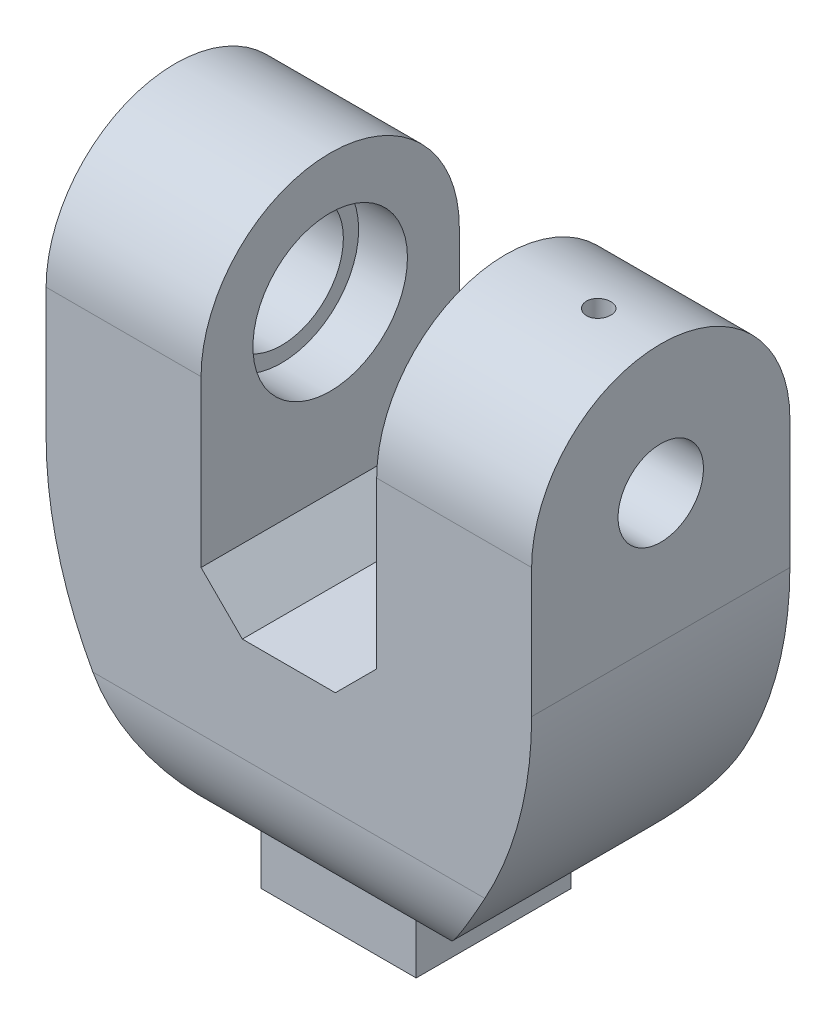
SolidWorks part; units mm, degrees
material "PLA"
ref_plane "Front Plane" through (0, 0, 0) normal (0, 0, 1) x (1, 0, 0)
ref_plane "Top Plane" through (0, 0, 0) normal (0, 1, 0) x (1, 0, 0)
ref_plane "Right Plane" through (0, 0, 0) normal (1, 0, 0) x (0, 0, -1)
sketch "Sketch1" plane through (0, 0, 0) normal (1, 0, 0) x (0, 0, -1)
  circle A0 centre (0, 0) radius 3 construction
  circle A1 centre (0, 0) radius 9.5
  circle A2 centre (0, 0) radius 15.875
  dimension "D1" = 6
  dimension "D2" = 19
  dimension "D3" = 31.75
extrude "Boss-Extrude1" add sketch "Sketch1" along normal blind 6
sketch "Sketch2" plane through (0, 0, 0) normal (-1, 0, 0) x (0, 0, 1)
  circle A0 centre (0, 0) radius 9.5 construction
  circle A1 centre (0, 0) radius 15.875
  circle A2 centre (0, 0) radius 15.875
  circle A3 centre (0, 0) radius 9.5
  circle A4 centre (0, 0) radius 7.62
  circle M3 centre (0, 0) radius 15.875
  circle M4 centre (0, 0) radius 9.5
  dimension "D2" = 15.24
  dimension "D1" = 0
extrude "Boss-Extrude2" add sketch "Sketch2" along normal blind 13.05 contours A4 M4 | M3 M4 region at (0, 0, -15.426) region at (0, 0, -9.2313)
ref_plane "Plane1" through (16.795, 0, 0) normal (1, 0, 0) x (0, 0, -1)
mirror "Mirror2" about plane through (16.795, 0, 0) normal (1, 0, 0) of bodies 102
sketch "Sketch3" plane through (6, 0, 0) normal (1, 0, 0) x (0, 0, -1)
  line L0 (-15.875, 0) -> (-15.875, -38.1)
  line L1 (15.875, 0) -> (15.875, -38.1)
  arc A0 (-15.875, -38.1) -> (15.875, -38.1) centre (0, -38.1) ccw
  circle A1 centre (0, 0) radius 15.875
  circle A2 centre (0, 0) radius 15.875
  circle M2 centre (0, 0) radius 15.875
  dimension "D2" = 38.1
  dimension "D3" = 15.875
  dimension "D1" = 0
extrude "Boss-Extrude3" add sketch "Sketch3" against normal up to surface (19.05 mm away) contours L0 A0 L1 M2 region at (6, -31.5182, 0) up to face at (-13.05, 0, 7.62)
extrude "Boss-Extrude4" add sketch "Sketch3<3>" along normal up to surface (40.64 mm away) from surface contours L0 A0 L1 M2 region at (6, -31.5182, 0) up to face at (46.64, 0, 7.62) starting at face at (27.59, 0, -15.875)
sketch "Sketch3<3>" plane through (6, 0, 0) normal (1, 0, 0) x (0, 0, -1) same geometry as "Sketch3"
sketch "Sketch4" plane through (6, 0, 0) normal (1, 0, 0) x (0, 0, -1)
  line L0 (-15.875, -25.4) -> (15.875, -25.4)
  line L2 (-15.875, 0) -> (-15.875, -38.1)
  line L3 (15.875, -38.1) -> (15.875, 0)
  line L4 (-15.875, 0) -> (-15.875, -38.1)
  line L5 (15.875, -38.1) -> (15.875, 0)
  arc A2 (15.875, 0) -> (-15.875, 0) centre (0, 0) ccw
  arc A3 (-15.875, -38.1) -> (15.875, -38.1) centre (0, -38.1) ccw
  arc A4 (15.875, 0) -> (-15.875, 0) centre (0, 0) ccw
  arc A5 (-15.875, -38.1) -> (15.875, -38.1) centre (0, -38.1) ccw
  line M7 (-15.875, 0) -> (-15.875, -38.1)
  arc M8 (-15.875, -38.1) -> (15.875, -38.1) centre (0, -38.1) ccw
  line M9 (15.875, -38.1) -> (15.875, 0)
  dimension "D2" = 25.4
  dimension "D1" = 0
extrude "Boss-Extrude5" add sketch "Sketch4" along normal up to surface (21.59 mm away) contours L0 M7 M8 M9 region at (6, -38.2335, 0) up to face at (27.59, -19.05, 0)
sketch "Sketch5" plane through (0, 0, 15.875) normal (0, 0, 1) x (1, 0, 0)
  line L0 (6, -15.875) -> (-13.05, -15.875) construction
  line L2 (-13.05, -38.1) -> (-13.05, -53.975) construction
  line L8 (6, 0) -> (-13.05, 0)
  line L9 (-13.05, 0) -> (-13.05, -38.1)
  line L10 (-13.05, -38.1) -> (46.64, -38.1)
  line L11 (46.64, -38.1) -> (46.64, 0)
  line L12 (46.64, 0) -> (27.59, 0)
  line L13 (27.59, 0) -> (27.59, -25.4)
  line L14 (27.59, -25.4) -> (6, -25.4)
  line L15 (6, -25.4) -> (6, 0)
  line L16 (6, 0) -> (-13.05, 0)
  line L17 (-13.05, 0) -> (-13.05, -38.1)
  line L18 (-13.05, -38.1) -> (46.64, -38.1)
  line L19 (46.64, -38.1) -> (46.64, 0)
  line L20 (46.64, 0) -> (27.59, 0)
  line L21 (27.59, 0) -> (27.59, -25.4)
  line L22 (27.59, -25.4) -> (6, -25.4)
  line L23 (6, -25.4) -> (6, 0)
  line L25 (-13.05, -38.1) -> (-13.05, -53.975)
  line L26 (-13.05, -53.975) -> (46.64, -53.975)
  line L27 (46.64, -53.975) -> (46.64, -38.1)
  line L28 (-13.05, -15.875) -> (7.27, -53.975)
  line L29 (46.64, -15.875) -> (26.32, -53.975)
  line L30 (-13.05, -53.975) -> (46.64, -53.975) construction
  line L31 (16.795, -17.4625) -> (16.795, 17.4625) construction
  arc A0 (-13.05, -15.875) -> (7.27, -53.975) centre (32.8287, -15.875) ccw
  arc A1 (46.64, -15.875) -> (26.32, -53.975) centre (0.7613, -15.875) cw
  line M14 (-13.05, -38.1) -> (46.64, -38.1)
  line M15 (46.64, -38.1) -> (46.64, 0)
  dimension "D2" = 15.875
  dimension "D3" = 19.05
  dimension "D1" = 0
extrude "Cut-Extrude1" cut sketch "Sketch5" against normal through all contours L28 L25 L26 M14 | L28 L17 M14 | L29 L26 L27 M14 | L29 M15 M14 region at (-11.3474, -32.6157, 15.875) region at (-6.3907, -47.6285, 15.875) region at (44.9374, -32.6157, 15.875) region at (39.9807, -47.6285, 15.875)
sketch "Sketch9" plane through (0, -25.4, 0) normal (0, 1, 0) x (1, 0, 0)
  line L0 (5.7854, 0) -> (27.3575, 0) construction
  line L1 (16.795, 15.875) -> (16.795, -15.875) construction
  line L2 (27.59, 15.875) -> (6, 15.875) construction
  line L4 (27.59, -15.875) -> (27.59, 15.875)
  line L5 (27.59, 15.875) -> (6, 15.875)
  line L6 (6, 15.875) -> (6, -15.875)
  line L7 (6, -15.875) -> (27.59, -15.875)
  line L8 (27.59, -15.875) -> (27.59, 15.875)
  line L9 (27.59, 15.875) -> (6, 15.875)
  line L10 (6, 15.875) -> (6, -15.875)
  line L11 (6, -15.875) -> (27.59, -15.875)
  line L12 (7.0465, -9.525) -> (26.0965, -9.525)
  line L13 (7.0465, -9.525) -> (7.0465, 9.525)
  line L14 (7.0465, 9.525) -> (26.0965, 9.525)
  line L15 (26.0965, -9.525) -> (26.0965, 9.525)
  line L16 (7.0465, -9.525) -> (26.0965, 9.525) construction
  line L17 (7.0465, 9.525) -> (26.0965, -9.525) construction
  point P12 (16.5715, 0)
  dimension "D2" = 19.05
  dimension "D1" = 0
extrude "Boss-Extrude8" add sketch "Sketch9" against normal blind 31.75 contours L12 L15 L14 L13 region at (16.5715, -25.4, 0)
chamfer "Chamfer1" distance 5.08 angle 45 2 edges at (27.59, -25.4, 0) (6, -25.4, 0)
sketch "Sketch6" plane through (46.64, 0, 0) normal (1, 0, 0) x (0, 0, -1)
  line L3 (-15.875, 0) -> (-15.875, -15.875)
  line L4 (-15.875, -15.875) -> (15.875, -15.875)
  line L5 (15.875, -15.875) -> (15.875, 0)
  line L6 (-15.875, 0) -> (-15.875, -15.875)
  line L8 (15.875, -15.875) -> (15.875, 0)
  line L9 (-15.875, -15.875) -> (15.875, -15.875)
  circle A0 centre (0, 0) radius 7.62 construction
  arc A1 (15.875, 0) -> (-15.875, 0) centre (0, 0) ccw
  arc A2 (15.875, 0) -> (-15.875, 0) centre (0, 0) ccw
  circle A3 centre (0, 0) radius 7.62
  circle A4 centre (0, 0) radius 5.25
  circle M14 centre (0, 0) radius 7.62
  dimension "D2" = 10.5
  dimension "D1" = 0
extrude "Boss-Extrude6" add sketch "Sketch6" against normal up to surface (13.05 mm away) contours A4 M14 region at (46.64, 0, 7.4045) up to face at (33.59, 0, 7.62)
sketch "Sketch7" plane through (-13.05, 0, 0) normal (-1, 0, 0) x (0, 0, 1)
  line L0 (0, 0) -> (0, 12.7) construction
  line L3 (-15.875, 0) -> (-15.875, -15.875)
  line L4 (-15.875, -15.875) -> (15.875, -15.875)
  line L5 (15.875, -15.875) -> (15.875, 0)
  line L6 (-15.875, 0) -> (-15.875, -15.875)
  line L8 (15.875, -15.875) -> (15.875, 0)
  line L10 (-15.875, -15.875) -> (15.875, -15.875)
  circle A0 centre (0, 0) radius 7.62 construction
  arc A1 (15.875, 0) -> (-15.875, 0) centre (0, 0) ccw
  arc A2 (15.875, 0) -> (-15.875, 0) centre (0, 0) ccw
  circle A3 centre (0, 0) radius 7.62
  circle A4 centre (0, 12.7) radius 1.5
  circle A5 centre (0, -12.7) radius 1.5
  dimension "D2" = 3
  dimension "D5" = 3
  dimension "D3" = 12.7
  dimension "D4" = 12.7
  dimension "D1" = 0
extrude "Cut-Extrude2" cut sketch "Sketch7" against normal blind 12.7 contours A4 | A5 region at (-13.05, 12.7, 0) region at (-13.05, -12.7, 0)
ref_plane "Plane2" through (0, 15.875, 0) normal (0, 1, 0) x (1, 0, 0)
sketch "Sketch8" plane through (0, 15.875, 0) normal (0, 1, 0) x (1, 0, 0)
  line L0 (46.64, -15.875) -> (46.64, 15.875) construction
  circle A0 centre (39.02, 0) radius 1.5
  dimension "D1" = 3
  dimension "D2" = 7.62
extrude "Cut-Extrude3" cut sketch "Sketch8" against normal up to surface (10.8438 mm away) up to face at (33.59, 0, -5.25)
